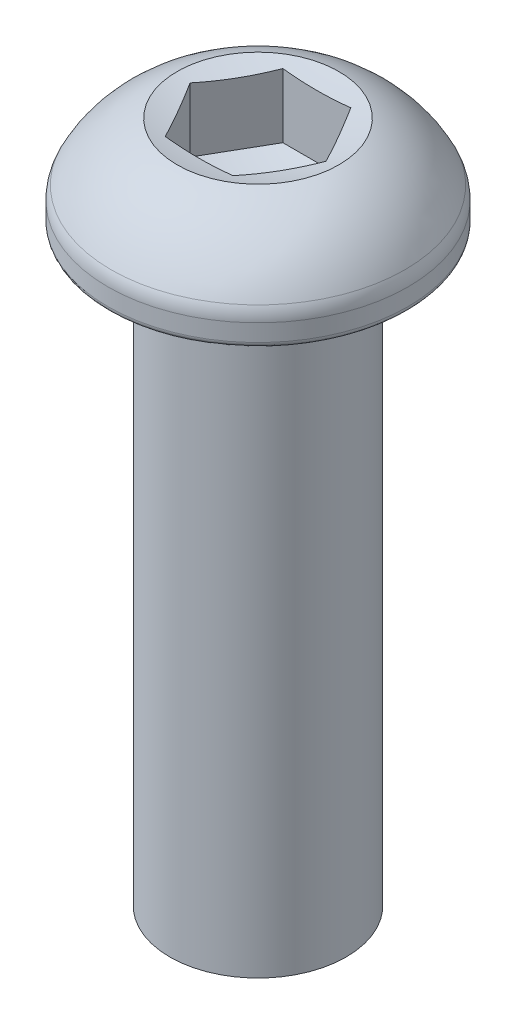
SolidWorks part; units mm, degrees
note: '?' marks a value the reader was unsure of.
material "304 STAINLESS STEEL"
ref_plane "Front Plane" through (0, 0, 0) normal (0, 0, 1) x (1, 0, 0)
ref_plane "Top Plane" through (0, 0, 0) normal (0, 1, 0) x (1, 0, 0)
ref_plane "Right Plane" through (0, 0, 0) normal (1, 0, 0) x (0, 0, -1)
ref_axis "X-Axis" through (-88.99, 0, 0) along (1, 0, 0)?
ref_axis "Y-Axis" through (0, 55, 0) along (0, -1, 0)
ref_axis "Z-Axis" through (0, 0, -88.99) along (0, 0, 1)?
sketch "Sketch1" plane through (0, 0, 0) normal (0, 0, 1) x (1, 0, 0)
  line L0 (0, 0) -> (5.1, 0)
  line L1 (5.1, 0) -> (5.1, 1)
  line L2 (0, 0) -> (0, 3.2)
  line L3 (0, 3.2) -> (2.75, 3.2)
  arc A0 (2.75, 3.2) -> (5.1, 1) centre (1.4224, -0.5733) cw
  dimension "D5" = 4
  dimension "D1" = 5.1
  dimension "D2" = 3.2
  dimension "D3" = 2.75
  dimension "D4" = 1
revolve "Revolve1" add sketch "Sketch1" angle 360 about axis through (0, 55, 0) along (0, -1, 0)
fillet "Fillet1" radius 0.2 1 edges at (0, 0, 5.1)
fillet "Fillet2" radius 1 1 edges at (0, 1, 5.1)
sketch "Sketch2" plane through (0, 0, 0) normal (0, -1, 0) x (1, 0, 0)
  circle A0 centre (0, 0) radius 3
  dimension "D1" = 6
extrude "Boss-Extrude1" add sketch "Sketch2" along normal blind 20
thread "Thread1" [suppressed] pitch 1 start angle 0, offset 2, length 0, pitch 1, diameter 6
ref_plane "Plane1" through (3, -22, 0) normal (0, 0, 1) x (1, 0, 0)
sketch "Thread Profile1" plane through (3, -22, 0) normal (0, 0, 1) x (1, 0, 0)
  line L0 (0, 0) -> (0, 1) construction
  line L11 (0, 0) -> (0, 0.875)
  line L12 (0, 0.875) -> (-0.5413, 0.5625)
  line L13 (-0.5413, 0.5625) -> (-0.5413, 0.3125)
  line L15 (-0.5413, 0.3125) -> (0, 0)
  line L17 (-0.5413, 0.4375) -> (0, 0.4375) construction
  point P2 (0, 0)
  dimension "Pitch" = 1
  dimension "Profile_Angle" = 60
  dimension "Profile_Land" = 0.25
  dimension "Profile_Height" = 0.5413
sketch "Sketch6" plane through (0, 0, 0) normal (0, 0, 1) x (1, 0, 0)
  line L0 (0, 0) -> (0, 3.2)
  line L1 (2.75, 3.2) -> (-2.75, 3.2) construction
  line L2 (0, 3.2) -> (2.75, 3.2)
  line L3 (0, 0) -> (4.9, 0)
  line L4 (4.9, 0) -> (2.75, 3.2)
  arc A0 (4.9925, 1.2306) -> (2.75, 3.2) centre (1.4224, -0.5733) ccw construction
revolve "Revolve2" add sketch "Sketch6" angle 360 about axis through (0, 55, 0) along (0, -1, 0)
sketch "Sketch7" plane through (0, 3.2, 0) normal (0, 1, 0) x (1, 0, 0)
  line L1 (1.1547, -2) -> (2.3094, 0)
  line L2 (2.3094, 0) -> (1.1547, 2)
  line L3 (1.1547, 2) -> (-1.1547, 2)
  line L4 (-1.1547, 2) -> (-2.3094, 0)
  line L5 (-2.3094, 0) -> (-1.1547, -2)
  line L6 (-1.1547, -2) -> (1.1547, -2)
  circle A0 centre (0, 0) radius 2 construction
  dimension "D1" = 4
extrude "Cut-Extrude1" cut sketch "Sketch7" against normal blind 2.3
sketch "Sketch8" plane through (0, 0, 0) normal (0, 0, 1) x (1, 0, 0)
  line L0 (0, 0.9) -> (0, 0.5)
  line L1 (0, 0.9) -> (2.3094, 0.9)
  line L2 (1.1547, 0.9) -> (-1.1547, 0.9) construction
  line L3 (1.1547, 0.9) -> (-1.1547, 0.9) construction
  line L4 (-2.3094, 0.9) -> (-2.3094, 3.2) construction
  line L5 (-2.3094, 0.9) -> (-2.3094, 3.2) construction
  line L6 (2.3094, 0.9) -> (2.3094, 3.2) construction
  line L7 (2.3094, 0.9) -> (2.3094, 3.2) construction
  line L8 (0, 0.5) -> (0.25, 0.5)
  arc A1 (0.25, 0.5) -> (2.3094, 0.9) centre (0.25, 6.0014) ccw
  dimension "D2" = 0.25
  dimension "D1" = 0.4
revolve "Cut-Revolve1" cut sketch "Sketch8" angle 360 about axis through (0, 55, 0) along (0, -1, 0)
sketch "Sketch9" plane through (0, 0, 0) normal (0, 0, 1) x (1, 0, 0)
  line L0 (2.75, 3.2) -> (-2.75, 3.2) construction
  line L1 (2.75, 3.2) -> (-2.75, 3.2)
  line L2 (0, 3.2) -> (0, 2.8144)
  line L3 (0, 2.8144) -> (-2.75, 2.8144) construction
  arc A0 (2.75, 3.2) -> (0, 2.8144) centre (0, 12.8144) cw
  dimension "D1" = 10
revolve "Cut-Revolve2" cut sketch "Sketch9" angle 360 about axis through (0, 55, 0) along (0, -1, 0)
sketch "Sketch10" [suppressed] plane through (0, 0, 0) normal (0, 0, 1) x (1, 0, 0)
  line L0 (3, -19.6) -> (3, -20)
  line L1 (3, -20) -> (2.4, -20)
  line L2 (2.4, -20) -> (3, -19.6)
  line L3 (-2.2716, -20) -> (2.1213, -20) construction
  line L4 (3, -19.125) -> (3, -19) construction
  dimension "D1" = 0.4
  dimension "D2" = 0.6
revolve "Cut-Revolve3" [suppressed] cut sketch "Sketch10" angle 360 about axis through (0, 55, 0) along (0, -1, 0)
